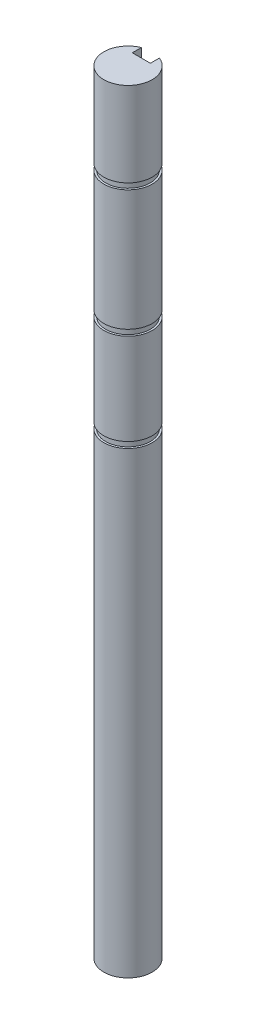
SolidWorks part; units mm, degrees
note: The reader was unsure of these and kept them because the rebuilt part matched: shared geometry of "Sketch3<3>", "Sketch3<4>".
material "1023 Carbon Steel Sheet (SS)"
ref_plane "Front Plane" through (0, 0, 0) normal (0, 0, 1) x (1, 0, 0)
ref_plane "Top Plane" through (0, 0, 0) normal (0, 1, 0) x (1, 0, 0)
ref_plane "Right Plane" through (0, 0, 0) normal (1, 0, 0) x (0, 0, -1)
sketch "Sketch1" plane through (0, 0, 0) normal (0, 1, 0) x (1, 0, 0)
  line L0 (-1.1906, 2.9433) -> (-1.1906, 1.7527)
  line L1 (-1.1906, 1.7527) -> (1.1906, 1.7527)
  line L2 (1.1906, 1.7527) -> (1.1906, 2.9433)
  arc A0 (-1.1906, 2.9433) -> (1.1906, 2.9433) centre (0, 0) ccw
  point P5 (0, 1.7527)
  dimension "D1" = 6.35
  dimension "D2" = 2.3813
  dimension "D3" = 1.1906
extrude "Boss-Extrude1" add sketch "Sketch1" along normal blind 101.6
sketch "Sketch3" plane through (0, 101.6, 0) normal (0, 1, 0) x (1, 0, 0)
  circle A0 centre (0, 0) radius 2.921
  circle A1 centre (0, 0) radius 3.175
  arc A2 (-1.1906, 2.9433) -> (1.1906, 2.9433) centre (0, 0) ccw construction
  dimension "D1" = 0.254
extrude "Cut-Extrude1" cut sketch "Sketch3" along normal blind 0.7874 from offset 41.3258 offset against normal yes
extrude "Cut-Extrude2" cut sketch "Sketch3<3>" along normal blind 0.7874 from offset 28.5496 offset against normal yes
sketch "Sketch3<3>" plane through (0, 101.6, 0) normal (0, 1, 0) x (1, 0, 0) same geometry as "Sketch3"
extrude "Cut-Extrude3" cut sketch "Sketch3<4>" along normal blind 0.7874 from offset 11.8872
sketch "Sketch3<4>" plane through (0, 101.6, 0) normal (0, 1, 0) x (1, 0, 0) same geometry as "Sketch3"
